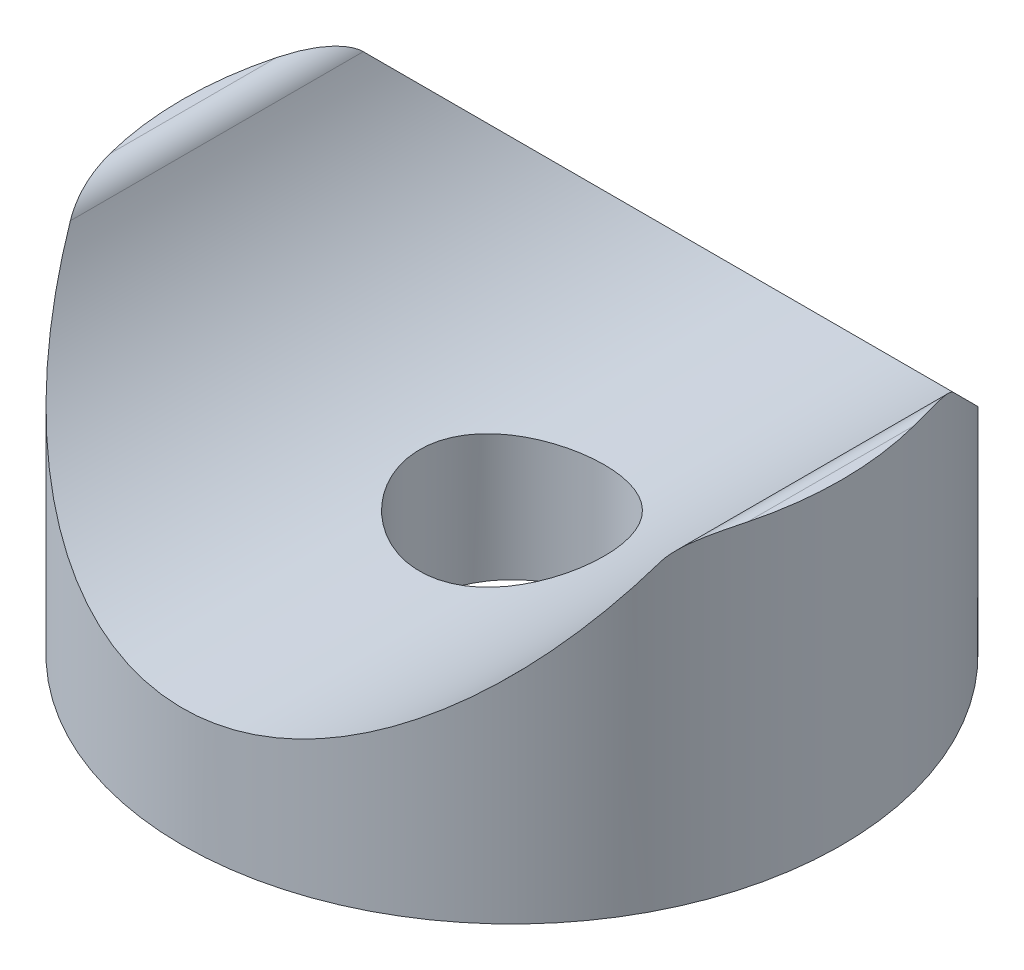
SolidWorks part; units mm, degrees
ref_plane "Front Plane" through (0, 0, 0) normal (0, 0, 1) x (1, 0, 0)
ref_plane "Top Plane" through (0, 0, 0) normal (0, 1, 0) x (1, 0, 0)
ref_plane "Right Plane" through (0, 0, 0) normal (1, 0, 0) x (0, 0, -1)
sketch "Sketch1" plane through (0, 0, 0) normal (0, 1, 0) x (1, 0, 0)
  circle A0 centre (0, 0) radius 12.5
  circle A1 centre (0, 0) radius 3.5
  dimension "D1" = 25
extrude "Boss-Extrude1" add sketch "Sketch1" along normal blind 12
sketch "Sketch2" plane through (0, 0, 0) normal (0, 0, 1) x (1, 0, 0)
  line L1 (0, 17) -> (0, 12) construction
  line L2 (12.5, 12) -> (-12.5, 12) construction
  circle A0 centre (0, 17) radius 12.5
  dimension "D1" = 25
  dimension "D2" = 5
extrude "Cut-Extrude1" cut sketch "Sketch2" against normal blind 22 and the other way blind 22
fillet "Fillet2" radius 1 2 edges at (11.4564, 12, 0) (-11.4564, 12, 0)
